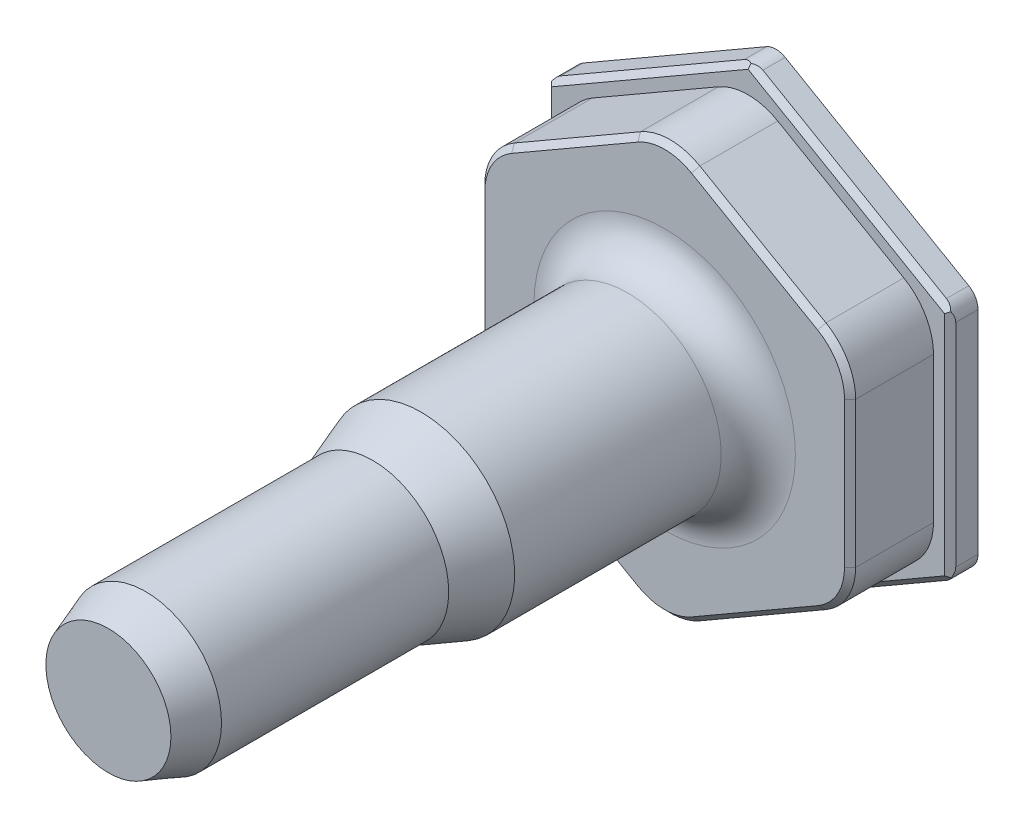
SolidWorks part; units mm, degrees
ref_plane "Front Plane" through (0, 0, 0) normal (0, 0, 1) x (1, 0, 0)
ref_plane "Top Plane" through (0, 0, 0) normal (0, 1, 0) x (1, 0, 0)
ref_plane "Right Plane" through (0, 0, 0) normal (1, 0, 0) x (0, 0, -1)
sketch "Sketch1" plane through (0, 0, 0) normal (0, 0, 1) x (1, 0, 0)
  line L12 (0, 11.547) -> (10, 5.7735)
  line L14 (10, 5.7735) -> (10, -5.7735)
  line L15 (10, -5.7735) -> (0, -11.547)
  line L16 (0, -11.547) -> (-10, -5.7735)
  line L17 (-10, -5.7735) -> (-10, 5.7735)
  line L18 (-10, 5.7735) -> (0, 11.547)
  line L19 (-10.9, 6.2931) -> (0, 12.5862)
  line L20 (0, 12.5862) -> (10.9, 6.2931)
  line L21 (10.9, 6.2931) -> (10.9, -6.2931)
  line L22 (10.9, -6.2931) -> (0, -12.5862)
  line L23 (0, -12.5862) -> (-10.9, -6.2931)
  line L24 (-10.9, -6.2931) -> (-10.9, 6.2931)
  circle A1 centre (0, 0) radius 3.25
  circle A2 centre (0, 0) radius 5.05
  circle A3 centre (0, 0) radius 2.125
  circle A4 centre (0, 0) radius 4.1
  point P3 (0, 11.547)
  point P4 (10, 5.7735)
  point P7 (10, -5.7735)
  point P9 (0, -11.547)
  point P10 (-10, -5.7735)
  point P12 (-10, 5.7735)
  point P13 (0, 0)
  dimension "D1" = 20
  dimension "D6" = 6.5
  dimension "D7" = 10.1
  dimension "D8" = 4.25
  dimension "D9" = 8.2
  dimension "D2" = 6
  dimension "D3" = 120
  dimension "D4" = 120
  dimension "D5" = 0.9
extrude "Boss-Extrude1" add sketch "Sketch1" along normal blind 1.5 contours L19 L20 L21 L22 L23 L24
ref_plane "Plane1" through (-10.9, -6.2931, 0) normal (-0.866, 0.5, 0) x (0, 0, 1)
ref_plane "Plane2" through (0, -12.5862, 0) normal (-0.866, 0.5, 0) x (0, 0, 1)
extrude "Boss-Extrude3" add sketch "Sketch1<8>" along normal blind 36 contours A4
sketch "Sketch1<8>" plane through (0, 0, 0) normal (0, 0, 1) x (1, 0, 0) same geometry as "Sketch1"
extrude "Boss-Extrude4" add sketch "Sketch1<9>" along normal blind 19 contours A2
sketch "Sketch1<9>" plane through (0, 0, 0) normal (0, 0, 1) x (1, 0, 0) same geometry as "Sketch1"
shell "Shell1" thickness 2
extrude "Cut-Extrude1" cut sketch "Sketch1<10>" along normal blind 17 contours A1
sketch "Sketch1<10>" plane through (0, 0, 0) normal (0, 0, 1) x (1, 0, 0) same geometry as "Sketch1"
extrude "Boss-Extrude2" add sketch "Sketch1<3>" along normal blind 6 contours L17 L18 L12 L14 L15 L16 | A1
sketch "Sketch1<3>" plane through (0, 0, 0) normal (0, 0, 1) x (1, 0, 0) same geometry as "Sketch1"
chamfer "Chamfer1" distance 2 angle 20 1 edges at (4.1, 0, 36) first distance on face at (4.1, 0, 19)
chamfer "Chamfer2" distance 1 angle 70 1 edges at (4.1, 0, 19) first distance on face at (4.1, 0, 19)
chamfer "Chamfer3" distance 0.7 angle 60 1 edges at (2.1, 0, 17) first distance on face at (2.1, 0, 17)
chamfer "Chamfer6" distance 0.3 angle 45 1 edges at (3.25, 0, 0)
ref_plane "Plane3" through (0, 0, 5) normal (0, 0, 1) x (1, 0, 0)
sketch "Sketch2" plane through (0, 0, 5) normal (0, 0, 1) x (1, 0, 0)
  line L1 (-17.7118, 13.112) -> (21.871, 13.112)
  line L2 (-17.7118, 13.112) -> (-17.7118, -17.4474)
  line L3 (-17.7118, -17.4474) -> (21.871, -17.4474)
  line L4 (21.871, 13.112) -> (21.871, -17.4474)
fillet "Fillet1" radius 3.2 6 edges at (10, -5.7735, 3.75) (0, -11.547, 3.75) (-10, -5.7735, 3.75) (-10, 5.7735, 3.75) (0, 11.547, 3.75) (10, 5.7735, 3.75)
chamfer "Chamfer5" distance 0.3 angle 45 18 edges at (-10, 0, 6) (-5, 8.6603, 6) (5, 8.6603, 6) (10, 0, 6) (5, -8.6603, 6) (-5, -8.6603, 6) (10.9, 0, 1.5) (5.45, -9.4397, 1.5) (-5.45, -9.4397, 1.5) (-10.9, 0, 1.5) (5.45, 9.4397, 1.5) (-5.45, 9.4397, 1.5) (0, -11.052, 6) (-9.5713, -5.526, 6) (-9.5713, 5.526, 6) (0, 11.052, 6) (9.5713, 5.526, 6) (9.5713, -5.526, 6)
fillet "Fillet2" radius 1 6 edges at (10.9, -6.2931, 0.6) (10.9, 6.2931, 0.6) (0, 12.5862, 0.6) (0, -12.5862, 0.6) (-10.9, -6.2931, 0.6) (-10.9, 6.2931, 0.6)
fillet "Fillet3" radius 2 1 edges at (-5.05, 0, 6)
